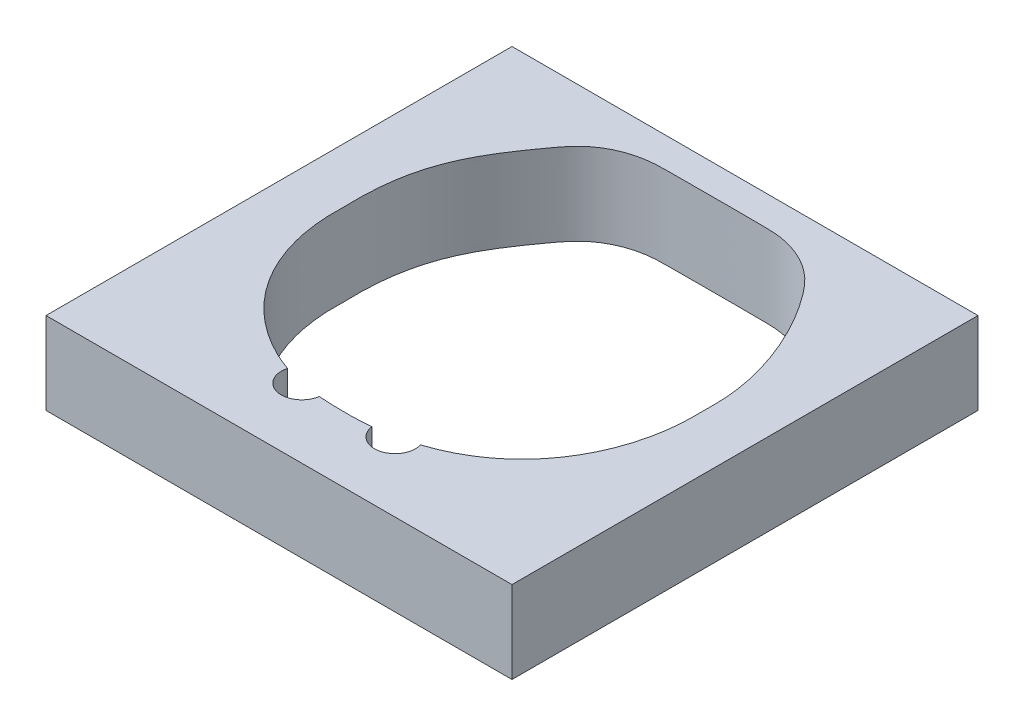
SolidWorks part; units mm, degrees
ref_plane "Plan de face" through (0, 0, 0) normal (0, 0, 1) x (1, 0, 0)
ref_plane "Plan de dessus" through (0, 0, 0) normal (0, 1, 0) x (1, 0, 0)
ref_plane "Plan de droite" through (0, 0, 0) normal (1, 0, 0) x (0, 0, -1)
ref_plane "Plan1" through (0, 0, 0) normal (0, 1, 0) x (1, 0, 0)
sketch "Esquisse1" plane through (0, 0, 0) normal (0, 1, 0) x (1, 0, 0)
  line L1 (-8.5, 8) -> (8.5, 8)
  line L2 (-8.5, 8) -> (-8.5, -9)
  line L3 (-8.5, -9) -> (8.5, -9)
  line L4 (8.5, 8) -> (8.5, -9)
  spline S0 degree 3 poles (-6.4938, -0.2013) (-6.572, 2.567) (-5.6328, 4.1026) (-3.9037, 6.4469) (-2.7582, 6.8993) (-0.8788, 6.9122) (1.1301, 6.9137) (2.7624, 6.8946) (3.9133, 6.3937) (5.6838, 4.1829) (6.5548, 1.8243) (6.4943, -0.0064) (6.5124, -0.675) (6.2456, -3.4367) (4.3253, -6.1825) (0.5423, -6.62) (-0.4249, -6.6075) (-3.0912, -6.4783) (-6.1228, -4.404) (-6.517, -0.7729) (-6.4938, -0.2013) (-6.572, 2.567) (-5.6328, 4.1026) knots -0.028087 -0.008777 -0.000975 0 0.112372 0.130276 0.173621 0.187169 0.252205 0.26694 0.319781 0.34342 0.479691 0.498677 0.514296 0.542967 0.756721 0.785787 0.80456 0.825241 0.971913 0.991223 0.999025 1 1.112372 1.130276 1.173621 only from (-6.5, 0.0214) to (-6.5, 0.0214)
  point P0 (-4.3092, 5.8708)
  point P1 (-2.0473, 6.9)
  point P2 (10, -12)
  point P3 (2.0473, 6.9)
  point P5 (4.3092, 5.8708)
  point P9 (6.5, 0.0214)
  point P11 (6.5, -0.6)
  point P13 (0.5, -6.6)
  point P15 (-0.5, -6.6)
  point P19 (-6.5, -0.6)
  point P21 (-6.5, 0.0214)
  dimension "D1" = 17
  dimension "D2" = 17
  dimension "D3" = 8.5
  dimension "D4" = 9
extrude "Boss.-Extru.1" add sketch "Esquisse1" along normal blind 3
sketch "Esquisse3" plane through (0, 3, 0) normal (0, 1, 0) x (1, 0, 0)
  line L0 (0, 0) -> (0, -3.4245) construction
  circle A0 centre (-1.7, -6.4677) radius 0.75
  circle A2 centre (1.7, -6.4677) radius 0.75
  spline S1 degree 3 poles (-5.6328, 4.1026) (-6.572, 2.567) (-6.4938, -0.2013) (-6.517, -0.7729) (-6.1228, -4.404) (-3.0912, -6.4783) (-0.4249, -6.6075) (0.5423, -6.62) (4.3253, -6.1825) (6.2456, -3.4367) (6.5124, -0.675) (6.4943, -0.0064) (6.5548, 1.8243) (5.6838, 4.1829) (3.9133, 6.3937) (2.7624, 6.8946) (1.1301, 6.9137) (-0.8788, 6.9122) (-2.7582, 6.8993) (-3.9037, 6.4469) (-5.6328, 4.1026) (-6.572, 2.567) (-6.4938, -0.2013) knots -0.173621 -0.130276 -0.112372 0 0.000975 0.008777 0.028087 0.174759 0.19544 0.214213 0.243279 0.457033 0.485704 0.501323 0.520309 0.65658 0.680219 0.73306 0.747795 0.812831 0.826379 0.869724 0.887628 1 1.000975 1.008777 1.028087 only from (-6.5, 0.0214) to (-6.5, 0.0214) construction
  dimension "D2" = 1.5
  dimension "D1" = 1.7
extrude "Enlèv. mat.-Extru.1" cut sketch "Esquisse3" against normal blind 3
equation "\"D3@Esquisse1\"=\"D2@Esquisse1\"/2"
